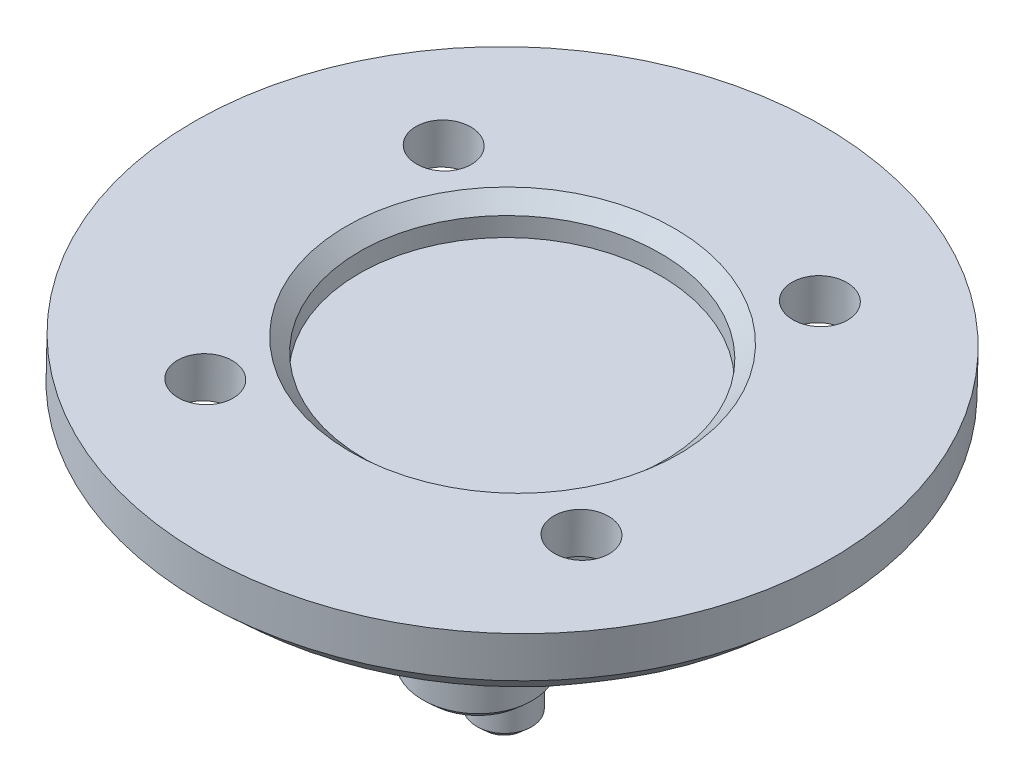
SolidWorks part; units mm, degrees
ref_plane "前视基准面" through (0, 0, 0) normal (0, 0, 1) x (1, 0, 0)
ref_plane "上视基准面" through (0, 0, 0) normal (0, 1, 0) x (1, 0, 0)
ref_plane "右视基准面" through (0, 0, 0) normal (1, 0, 0) x (0, 0, -1)
sketch "草图1" plane through (1.9667, 32.7154, 1.1083) normal (-0.06, -0.9976, -0.0338) x (0.9982, -0.0599, -0.002)
  circle A1 centre (-129.041, -30.648) radius 5.5
  circle A2 centre (-135.6095, -34.8139) radius 1
  circle A3 centre (-133.2068, -24.0795) radius 1
  circle A4 centre (-122.4724, -26.4821) radius 1
  circle A5 centre (-124.8751, -37.2165) radius 1
  circle A6 centre (-129.041, -30.648) radius 11.5
  dimension "D1" = 23
extrude "凸台-拉伸1" add sketch "草图1" along normal blind 2.5
sketch "草图2" plane through (1.8168, 30.2213, 1.0238) normal (-0.06, -0.9976, -0.0338) x (0.9982, -0.0599, -0.002)
  circle A0 centre (-129.041, -30.648) radius 5.5
extrude "凸台-拉伸2" add sketch "草图2" against normal blind 1.3
sketch "草图5" plane through (1.8168, 30.2213, 1.0238) normal (-0.06, -0.9976, -0.0338) x (0.9982, -0.0599, -0.002)
  circle A0 centre (-135.6095, -34.8139) radius 2.5
  circle A1 centre (-133.2068, -24.0795) radius 2.5
  circle A2 centre (-122.4724, -26.4821) radius 2.5
  circle A3 centre (-124.8751, -37.2165) radius 2.5
  point P12 (-129.041, -30.648)
  dimension "D1" = 4
  dimension "D2" = 5
extrude "切除-拉伸1" cut sketch "草图5" against normal blind 1
sketch "草图6" plane through (1.8168, 30.2213, 1.0238) normal (-0.06, -0.9976, -0.0338) x (0.9982, -0.0599, -0.002)
  circle A0 centre (-129.041, -29.648) radius 2
  dimension "D1" = 1
extrude "凸台-拉伸3" add sketch "草图6" along normal up to surface (7.5 mm away)
sketch "草图7" plane through (1.8168, 30.2213, 1.0238) normal (-0.06, -0.9976, -0.0338) x (0.9982, -0.0599, -0.002)
  circle A0 centre (-129.041, -29.648) radius 3
extrude "凸台-拉伸4" add sketch "草图7" along normal blind 4
sketch "草图10" plane through (1.367, 22.7391, 0.7703) normal (-0.06, -0.9976, -0.0338) x (0.9982, -0.0599, -0.002)
  circle A0 centre (-129.041, -30.648) radius 1
extrude "凸台-拉伸5" add sketch "草图10" along normal blind 2
chamfer "倒角1" distance 0.3 angle 45 3 edges at (-126.5635, 29.456, -29.6657) (-124.2372, 34.7891, -28.4804) (-129.4381, 31.5975, -28.5987)
sketch "草图11" plane through (1.5769, 26.2308, 0.8886) normal (-0.06, -0.9976, -0.0338) x (0.9982, -0.0599, -0.002)
  circle A0 centre (-129.041, -29.648) radius 2.3004
extrude "凸台-拉伸6" add sketch "草图11" along normal up to surface (1.5 mm away)
chamfer "倒角2" distance 1 angle 45 1 edges at (-115.5126, 38.3034, -29.3446)
chamfer "倒角3" distance 0.5 angle 45 4 edges at (-131.0531, 39.3782, -33.4948) (-128.6548, 38.8708, -22.7714) (-117.9397, 38.3087, -25.1945) (-120.3381, 38.8162, -35.9179)
chamfer "倒角4" distance 0.5 angle 45 1 edges at (-121.3519, 41.1575, -29.2602)
